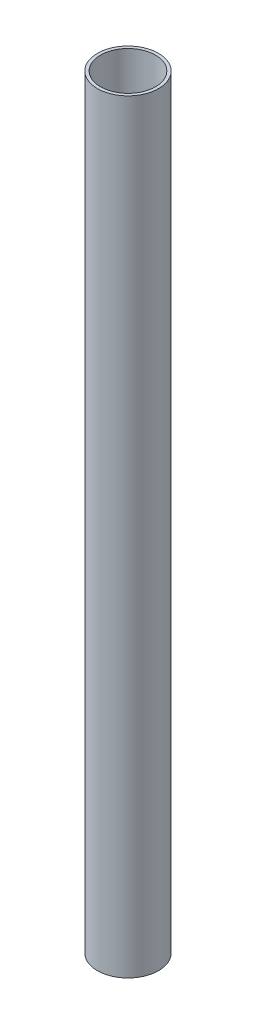
SolidWorks part; units mm, degrees
ref_plane "Front Plane" through (0, 0, 0) normal (0, 0, 1) x (1, 0, 0)
ref_plane "Top Plane" through (0, 0, 0) normal (0, 1, 0) x (1, 0, 0)
ref_plane "Right Plane" through (0, 0, 0) normal (1, 0, 0) x (0, 0, -1)
sketch "Sketch1" plane through (0, 0, 0) normal (0, 1, 0) x (1, 0, 0)
  circle A0 centre (0, 0) radius 10
  circle A1 centre (0, 0) radius 9
  dimension "D1" = 18
  dimension "D2" = 20
extrude "Boss-Extrude1" add sketch "Sketch1" along normal blind 250
